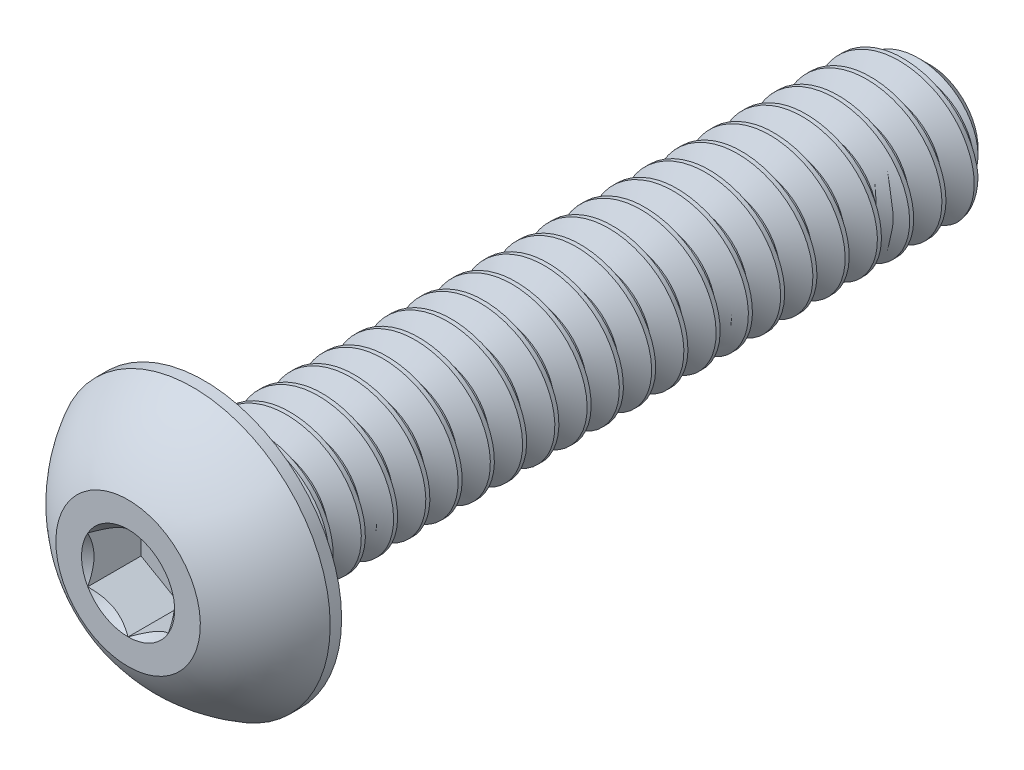
SolidWorks part; units mm, degrees
ref_plane "Front" through (0, 0, 0) normal (0, 0, 1) x (1, 0, 0)
ref_plane "Top" through (0, 0, 0) normal (0, 1, 0) x (1, 0, 0)
ref_plane "Right" through (0, 0, 0) normal (1, 0, 0) x (0, 0, -1)
sketch "Sketch1" plane through (0, 0, 0) normal (1, 0, 0) x (0, 0, -1)
  line L2 (1.4986, 1.4224) -> (15.7861, 1.4224)
  line L3 (15.7861, 1.4224) -> (15.7861, 0)
  line L4 (15.7861, 0) -> (1.4986, 0)
  line L6 (1.2738, 2.7051) -> (1.4986, 2.7051) construction
  line L7 (15.7861, 1.4224) -> (15.7861, -1.4224) construction
  line L8 (0, 0) -> (1.4986, 0) construction
  line L9 (1.4986, 2.7051) -> (1.4986, -2.7051) construction
  line L11 (1.4986, 1.4224) -> (1.4986, 0)
  line L13 (0, 0.7937) -> (0, -0.7937) construction
  line L14 (0, 0.7937) -> (0, 1.4224) construction
  arc A3 (0, 1.4224) -> (1.2738, 2.7051) centre (2.7151, 0) cw construction
  dimension "D1" = 0.2248
  dimension "Head Ht" = 1.4986
  dimension "Head Dia" = 5.4102
  dimension "Dia" = 2.8448
  dimension "Lg" = 14.2875
  dimension "Hex" = 1.5875
revolve "Revolve1" add sketch "Sketch1" angle 360 mid plane about L4
sketch "Sketch3" plane through (0, 0, -15.7861) normal (0, 0, -1) x (-1, 0, 0)
  circle A0 centre (0, 0) radius 1.4224
curve "Helix/Spiral1" pitch 0.635 height 14.9225 turns 23.5
sketch "Sketch2" plane through (0, 0, 0) normal (1, 0, 0) x (0, 0, -1)
  line L0 (15.7861, 1.4224) -> (16.3417, 1.4224)
  line L1 (16.3417, 1.4224) -> (16.1036, 1.01)
  line L2 (16.1036, 1.01) -> (16.0242, 1.01)
  line L3 (16.0242, 1.01) -> (15.7861, 1.4224)
  line L4 (15.9052, 1.2162) -> (16.2227, 1.2162) construction
  dimension "D1" = 60
  dimension "D2" = 0.0794
  dimension "D3" = 0.3175
chamfer "Chamfer1" distance 0.4763 angle 45 1 edges at (0, 1.4224, -15.7861)
sweep "Cut-Sweep1" cut profiles "Sketch2" path "Helix/Spiral1" align with end faces yes
sketch "Sketch7" plane through (0, 0, 0) normal (1, 0, 0) x (0, 0, -1)
  line L6 (1.2738, 2.7051) -> (1.4986, 2.7051) construction
  line L8 (0, 0) -> (1.4986, 0) construction
  line L11 (1.4986, 2.7051) -> (1.4986, -2.7051) construction
  line L12 (1.2738, 2.7051) -> (1.4986, 2.7051)
  line L13 (0, 0) -> (1.4986, 0)
  line L14 (0, 0.7937) -> (0, -0.7937) construction
  line L15 (1.4986, 2.7051) -> (1.4986, 0)
  line L16 (0, 1.4224) -> (0, 0)
  arc A2 (1.2738, 2.7051) -> (0, 1.4224) centre (2.7151, 0) ccw construction
  arc A3 (1.2738, 2.7051) -> (0, 1.4224) centre (2.7151, 0) ccw
revolve "Revolve2" add sketch "Sketch7" angle 360 mid plane about L13
sketch "Sketch5" plane through (0, 0, 0) normal (0, 0, 1) x (1, 0, 0)
  line L1 (0.7937, -0.4583) -> (0.7937, 0.4583)
  line L2 (0.7937, 0.4583) -> (0, 0.9165)
  line L3 (0, 0.9165) -> (-0.7937, 0.4583)
  line L4 (-0.7937, 0.4583) -> (-0.7937, -0.4583)
  line L5 (-0.7937, -0.4583) -> (0, -0.9165)
  line L6 (0, -0.9165) -> (0.7937, -0.4583)
  circle A0 centre (0, 0) radius 0.7937 construction
extrude "Cut-Extrude2" cut sketch "Sketch5" against normal blind 1.049
sketch "Sketch6" plane through (0, 0, 0) normal (0, 0, 1) x (1, 0, 0)
  circle A0 centre (0, 0) radius 0.9165
extrude "Cut-Extrude3" cut sketch "Sketch6" against normal blind 1.049 draft 45
sketch "Sketch9" [suppressed] plane through (0, 0, -1.4986) normal (0, 0, 1) x (1, 0, 0)
  circle A2 centre (0, 0) radius 1.4224
extrude "Boss-Extrude2" [suppressed] add sketch "Sketch9" against normal offset from surface (12.7 mm away) 31.75
sketch "Sketch10" plane through (0, 0, 0) normal (1, 0, 0) x (0, 0, -1)
  line L0 (15.7861, 1.4224) -> (15.7861, -1.4224) construction
  point P0 (14.8336, -1.4224)
  dimension "D1" = 0.9525
equation "\"D3@Helix/Spiral1\" = \"Lg@Sketch1\" + \"D4@Helix/Spiral1\""
equation "\"D2@Sketch2\" = \"D4@Helix/Spiral1\" * .125"
equation "\"D3@Sketch2\" = \"D4@Helix/Spiral1\" * .5"
equation "\"D1@Chamfer1\" = \"D4@Helix/Spiral1\" * .75"
equation "\"D1@Cut-Extrude2\" = \"Head Ht@Sketch1\" * .7"
equation "\"D1@Sketch1\" = \"Head Ht@Sketch1\" * .15"
equation "\"D1@Sketch10\" = \"D4@Helix/Spiral1\" * 1.5"
equation "\"D1@Cut-Extrude3\" = \"D1@Cut-Extrude2\""
